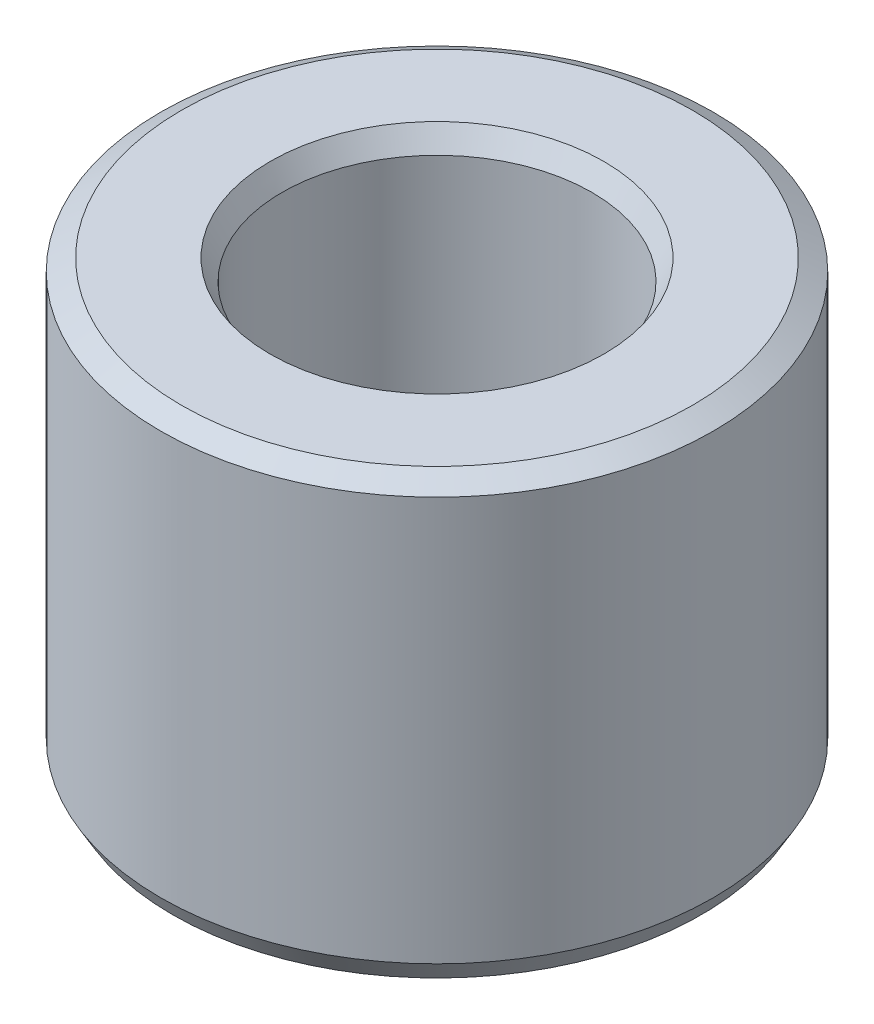
SolidWorks part; units mm, degrees
ref_plane "Front Plane" through (0, 0, 0) normal (0, 0, 1) x (1, 0, 0)
ref_plane "Top Plane" through (0, 0, 0) normal (0, 1, 0) x (1, 0, 0)
ref_plane "Right Plane" through (0, 0, 0) normal (1, 0, 0) x (0, 0, -1)
sketch "Sketch1" plane through (0, 0, 0) normal (0, 1, 0) x (1, 0, 0)
  circle A0 centre (0, 0) radius 55
  dimension "SLEEVE_OD" = 110
extrude "Boss-Extrude1" add sketch "Sketch1" along normal blind 86.9571
sketch "Sketch2" plane through (0, 0, 0) normal (0, 1, 0) x (1, 0, 0)
  circle A0 centre (0, 0) radius 30.832
  dimension "BORE_D" = 61.664
extrude "Cut-Extrude1" cut sketch "Sketch2" along normal through all
chamfer "Chamfer1" distance 2.3859 angle 60 4 edges at (0, 86.9571, 30.832) (0, 0, 30.832) (0, 0, 55) (0, 86.9571, 55) first distance on face at (0, 86.9571, 30.832) first distance on face at (0, 0, 30.832) first distance on face at (0, 86.9571, 55)
